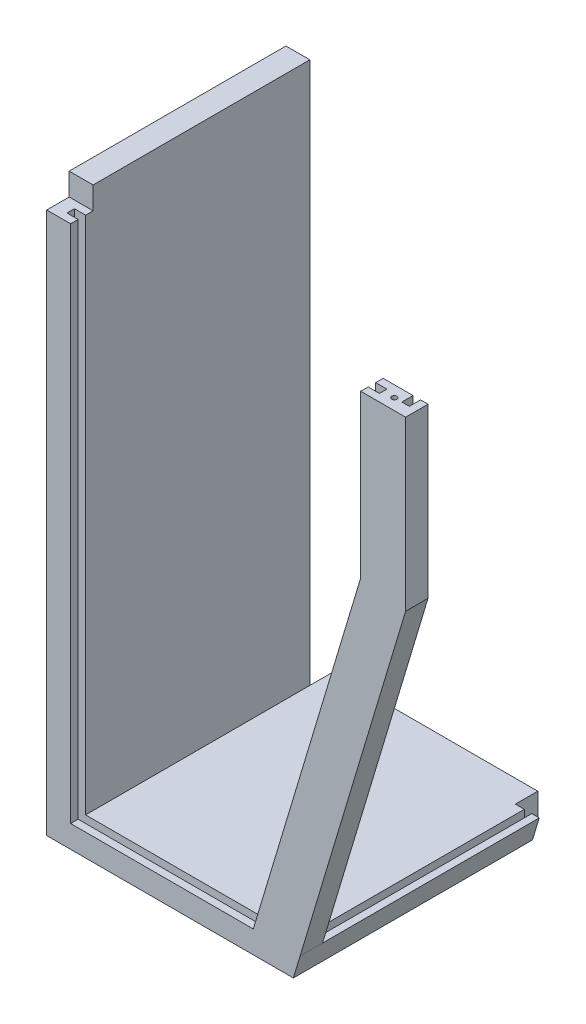
SolidWorks part; units mm, degrees
ref_plane "前视基准面" through (0, 0, 0) normal (0, 0, 1) x (1, 0, 0)
ref_plane "上视基准面" through (0, 0, 0) normal (0, 1, 0) x (1, 0, 0)
ref_plane "右视基准面" through (0, 0, 0) normal (1, 0, 0) x (0, 0, -1)
other "Configuration Table"
sketch "草图1" plane through (0, 0, 0) normal (0, 1, 0) x (1, 0, 0)
  line L1 (-60, -16) -> (60, -16)
  line L2 (-60, -16) -> (-60, 16)
  line L3 (-60, 16) -> (60, 16)
  line L4 (60, -16) -> (60, 16)
  line L5 (-60, -16) -> (60, 16) construction
  line L6 (-60, 16) -> (60, -16) construction
  point P0 (0, 0)
  dimension "D1" = 120
  dimension "D5" = 32
extrude "凸台-拉伸1" add sketch "草图1" along normal blind 3 contours L3 L4 L1 L2
sketch "草图2" plane through (0, 0, -16) normal (0, 0, -1) x (-1, 0, 0)
  line L0 (60, 0) -> (-60, 0) construction
  line L1 (56.8, 0) -> (29.3, 0)
  line L2 (56.8, 0) -> (56.8, 3)
  line L3 (56.8, 3) -> (29.3, 3)
  line L4 (29.3, 0) -> (29.3, 3)
  line L5 (60, 3) -> (-60, 3) construction
  line L6 (27, 0) -> (26.1, 3)
  line L8 (60, 3) -> (60, 0) construction
  point P10 (0, 0)
  line M6 (-60, 0) -> (60, 0)
  line M8 (60, 3) -> (-60, 3)
  line M9 (-60, 3) -> (-60, 0)
  dimension "D1" = 73.301
  dimension "D2" = 33
  dimension "D3" = 3.2
  dimension "D4" = 3.2
extrude "切除-拉伸1" cut sketch "草图2" against normal through all contours L6 M6 M8 M9 region at (16.7246, 1.4974, -16)
extrude "凸台-拉伸2" add sketch "草图2<3>" along normal blind 3 contours L1 L4 L3 L2
sketch "草图2<3>" plane through (0, 0, -16) normal (0, 0, -1) x (-1, 0, 0) same geometry as "草图2"
sketch "草图3" plane through (0, 3, 0) normal (0, 1, 0) x (1, 0, 0)
  line L0 (-56.8, 19) -> (-56.8, 16) construction
  line L1 (-56.8, 16) -> (-60, 16)
  line L2 (-56.8, 16) -> (-56.8, -16)
  line L3 (-56.8, -16) -> (-60, -16)
  line L4 (-60, 16) -> (-60, -16)
  line L5 (-60, 16) -> (-56.8, 16) construction
  line L6 (-60, -16) -> (-60, 16) construction
  line L7 (-60, -16) -> (-26.1, -16) construction
  point P10 (-60, -13.0903)
extrude "凸台-拉伸3" add sketch "草图3" along normal blind 72.5
sketch "草图4" plane through (0, 0, 16) normal (0, 0, 1) x (1, 0, 0)
  line L1 (-11.9849, 72.5) -> (-11.9849, 50.0007)
  line L2 (-11.9849, 50.0007) -> (-26.1, 3)
  line L3 (-56.8, 3) -> (-26.1, 3) construction
  line L4 (-27, 0) -> (-26.1, 3) construction
  line L5 (-26.1, 3) -> (-32.3647, 3)
  line L6 (-32.3647, 3) -> (-17.9849, 50.8822)
  line L8 (-56.8, 75.5) -> (-56.8, 3) construction
  line L9 (-60, 75.5) -> (-56.8, 75.5) construction
  line L10 (-11.9849, 72.5) -> (-17.9849, 72.5)
  line L11 (-17.9849, 72.5) -> (-17.9849, 50.8822)
  point P0 (-17.9849, 70.8959)
  line M9 (-26.1, 3) -> (-56.8, 3)
  line M10 (-56.8, 3) -> (-56.8, 75.5)
  dimension "D1" = 44.8151
  dimension "D2" = 6
  dimension "D3" = 163.284
  dimension "D4" = 6
  dimension "D5" = 3
extrude "凸台-拉伸4" add sketch "草图4" against normal blind 3 contours L6 L2 L1 M9 M10 region at (-19.9142, 37.4276, 16)
sketch "草图5" plane through (-56.8, 0, 0) normal (1, 0, 0) x (0, 0, -1)
  line L0 (-16, 75.5) -> (-16, 3) construction
  line L1 (-16, 72.5) -> (-13, 72.5)
  line L2 (-16, 72.5) -> (-16, 75.5)
  line L3 (-16, 75.5) -> (-13, 75.5)
  line L4 (-13, 72.5) -> (-13, 75.5)
  line L5 (-13, 72.5) -> (-16, 72.5) construction
  line L6 (-16, 75.5) -> (16, 75.5) construction
  line L7 (-13, 72.5) -> (-13, 50.0007) construction
extrude "切除-拉伸2" cut sketch "草图5" against normal through all
sketch "草图6" plane through (0, 3, 0) normal (0, 1, 0) x (1, 0, 0)
  line L0 (-32.3647, -13) -> (-32.3647, -16) construction
  line L1 (-32.3647, -15) -> (-56.8, -15)
  line L2 (-32.3647, -15) -> (-32.3647, -14)
  line L3 (-32.3647, -14) -> (-56.8, -14)
  line L4 (-56.8, -15) -> (-56.8, -14)
  line L5 (-56.8, -16) -> (-56.8, -13) construction
  line L6 (-32.3647, -14.5) -> (-56.8, -14.5) construction
  line L7 (-32.3647, -13) -> (-17.9849, -13) construction
  line L8 (-27.1, -13) -> (-28.1, -13)
  line L9 (-27.1, -13) -> (-27.1, 16)
  line L10 (-27.1, 16) -> (-28.1, 16)
  line L11 (-28.1, -13) -> (-28.1, 16)
  line L12 (-29.3, 16) -> (-26.1, 16) construction
  line L14 (-26.1, -13) -> (-26.1, 16) construction
  dimension "D1" = 1
  dimension "D2" = 1
  dimension "D3" = 1
extrude "切除-拉伸3" cut sketch "草图6" against normal blind 1.5
sketch "草图7" plane through (-56.8, 0, 0) normal (1, 0, 0) x (0, 0, -1)
  line L0 (-15, 1.5) -> (-15, 3) construction
  line L1 (-15, 1.5) -> (-14, 1.5)
  line L2 (-15, 1.5) -> (-15, 72.5)
  line L3 (-15, 72.5) -> (-14, 72.5)
  line L4 (-14, 1.5) -> (-14, 72.5)
  line L5 (-16, 72.5) -> (-13, 72.5) construction
  line L6 (-16, 72.5) -> (-16, 3) construction
  line L7 (-14, 1.5) -> (-15, 1.5) construction
  line L8 (-15, 50.0007) -> (-14, 50.0007)
  line L9 (-13, 50.0007) -> (-16, 50.0007) construction
  line M7 (-13, 72.5) -> (-16, 72.5)
  line M10 (-15, 3) -> (-15, 1.5)
  line M11 (-15, 1.5) -> (-14, 1.5)
  line M12 (-14, 1.5) -> (-14, 3)
  dimension "D1" = 1
  dimension "D2" = 1
extrude "切除-拉伸4" cut sketch "草图7" against normal blind 1.5 contours L4 L3 L2 L1
extrude "切除-拉伸6" cut sketch "草图7<4>" along normal offset from surface (25.551 mm away) 1.5 contours L8 L2 L4 M10 M11 M12 region at (-56.8, 25.7504, 14.5) up to face at (-27.5715, 18.9607, 14.5) offset beyond the face yes
sketch "草图7<4>" plane through (-56.8, 0, 0) normal (1, 0, 0) x (0, 0, -1) same geometry as "草图7"
extrude "切除-拉伸7" cut sketch "草图7<5>" along normal offset from surface (40.3151 mm away) 1.5 contours L2 L8 L4 M7 region at (-56.8, 61.2504, 14.5) up to face at (-17.9849, 61.6911, 14.5) offset beyond the face yes
sketch "草图7<5>" plane through (-56.8, 0, 0) normal (1, 0, 0) x (0, 0, -1) same geometry as "草图7"
sketch "草图9" plane through (0, 0, 13) normal (0, 0, -1) x (-1, 0, 0)
  line L0 (28.1, 1.5) -> (27.1, 1.5)
  line L1 (28.1, 1.5) -> (27.1, 1.5) construction
  line L2 (28.1, 1.5) -> (28.1, 3) construction
  line L3 (27.1, 1.5) -> (27.1, 3) construction
  line L4 (27.1, 1.5) -> (27.1, 3)
  line L5 (27.1, 3) -> (12.9849, 50.0007)
  line L6 (12.9849, 50.0007) -> (12.9849, 72.5)
  line L7 (12.9849, 72.5) -> (13.9849, 72.5)
  line L8 (13.9849, 72.5) -> (13.9849, 50.0007)
  line L9 (13.9849, 50.0007) -> (28.1, 3)
  line L11 (28.1, 3) -> (32.3647, 3) construction
  line L12 (28.1, 3) -> (28.1, 1.5)
  line L13 (11.9849, 50.0007) -> (26.1, 3) construction
  line L14 (26.1, 3) -> (27.1, 3) construction
  line L15 (11.9849, 72.5) -> (17.9849, 72.5) construction
  line L16 (11.9849, 72.5) -> (11.9849, 50.0007) construction
  point P8 (0, 0)
  point P19 (27.1, 4.4256)
  point P22 (0, 0)
  dimension "D1" = 1
  dimension "D2" = 1
extrude "切除-拉伸8" cut sketch "草图9" against normal blind 1.5
sketch "草图10" plane through (0, 72.5, 0) normal (0, 1, 0) x (1, 0, 0)
  line L0 (-11.9849, -16) -> (-17.9849, -16) construction
  line L1 (-11.9849, -13) -> (-11.9849, -16) construction
  circle A0 centre (-14.9849, -14.5) radius 0.35
  dimension "D1" = 0.7
  dimension "D2" = 1.5
  dimension "D3" = 3
extrude "切除-拉伸9" cut sketch "草图10" against normal blind 3
